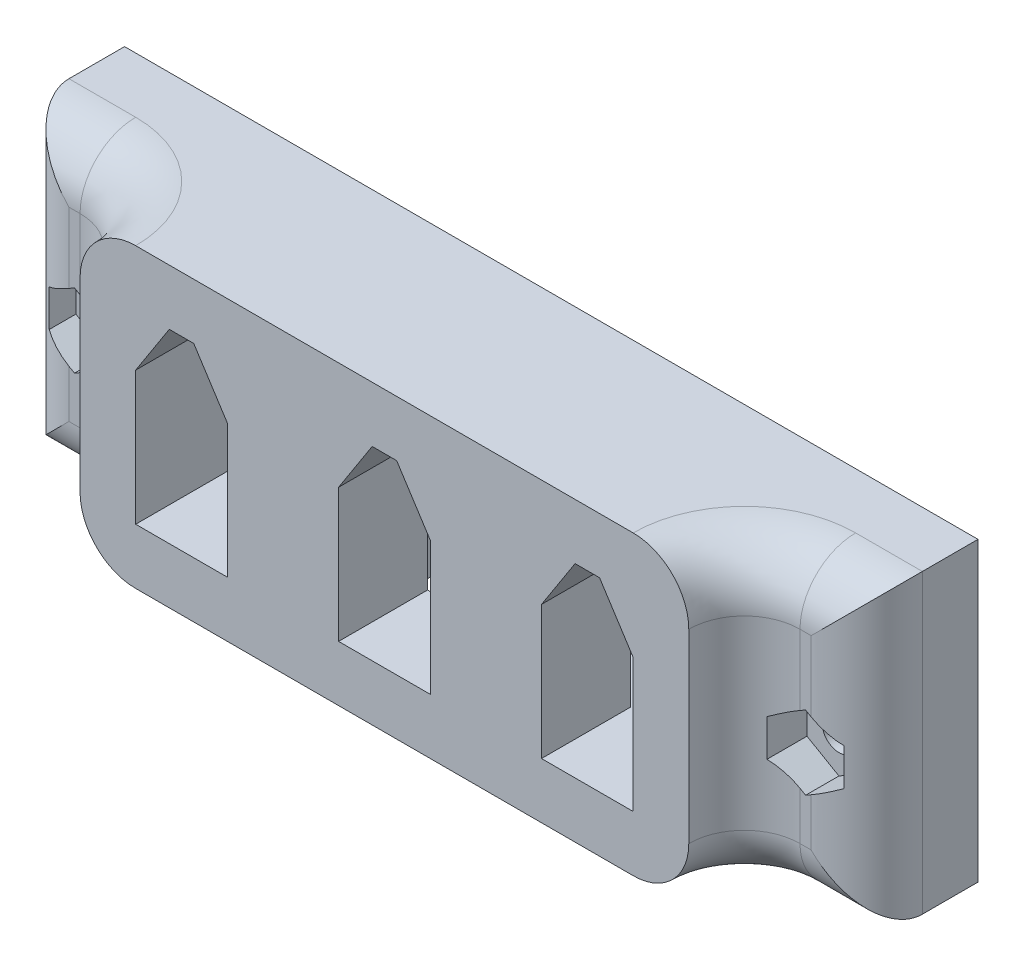
SolidWorks part; units mm, degrees
ref_plane "Front" through (0, 0, 0) normal (0, 0, 1) x (1, 0, 0)
ref_plane "Top" through (0, 0, 0) normal (0, 1, 0) x (1, 0, 0)
ref_plane "Right" through (0, 0, 0) normal (1, 0, 0) x (0, 0, -1)
sketch "Sketch1" plane through (0, 0, 0) normal (0, 0, 1) x (1, 0, 0)
  line L0 (0, 0) -> (0, 12)
  line L1 (0, 12) -> (3.02, 16.686)
  line L3 (8.24, 12) -> (8.24, 0)
  line L4 (0, 0) -> (8.24, 0)
  line L5 (3.02, 16.686) -> (5.22, 16.686)
  line L6 (5.22, 16.686) -> (8.24, 12)
  line L7 (23.46, 16.686) -> (26.48, 12)
  line L8 (26.48, 12) -> (26.48, 0)
  line L9 (18.24, 0) -> (26.48, 0)
  line L10 (18.24, 0) -> (18.24, 12)
  line L11 (18.24, 12) -> (21.26, 16.686)
  line L12 (21.26, 16.686) -> (23.46, 16.686)
  line L13 (41.7, 16.686) -> (44.72, 12)
  line L14 (44.72, 12) -> (44.72, 0)
  line L15 (36.48, 0) -> (44.72, 0)
  line L16 (36.48, 0) -> (36.48, 12)
  line L17 (36.48, 12) -> (39.5, 16.686)
  line L18 (39.5, 16.686) -> (41.7, 16.686)
  line L26 (-16, -5) -> (60.72, -5)
  line L27 (-16, -5) -> (-16, 21.686)
  line L28 (-16, 21.686) -> (60.72, 21.686)
  line L29 (60.72, -5) -> (60.72, 21.686)
  point P9 (4.12, 16.686)
  point P10 (4.12, 0)
  point P25 (22.36, 0)
  point P26 (22.36, -5)
  dimension "D1" = 8.24
  dimension "D2" = 16.686
  dimension "D3" = 2.2
  dimension "D4" = 12
  dimension "D6" = 10
  dimension "D7" = 5
  dimension "D8" = 5
  dimension "D9" = 16
  dimension "D5" = 3
extrude "Boss-Extrude1" add sketch "Sketch1" along normal blind 15
sketch "Sketch2" plane through (0, -5, 0) normal (0, -1, 0) x (-1, 0, 0)
  line L0 (-22.36, -15) -> (-22.36, 0) construction
  line L1 (16, -15) -> (-60.72, -15) construction
  line L2 (16, 0) -> (-60.72, 0) construction
  line L3 (-60.72, -15) -> (-60.72, 0) construction
  line L4 (16, -15) -> (5, -15)
  line L5 (16, -15) -> (16, -10)
  line L6 (16, -10) -> (5, -10)
  line L7 (5, -15) -> (5, -10)
  line L8 (-49.72, -15) -> (-60.72, -15)
  line L9 (-49.72, -15) -> (-49.72, -10)
  line L10 (-49.72, -10) -> (-60.72, -10)
  line L11 (-60.72, -15) -> (-60.72, -10)
  point P19 (0, 0)
  dimension "D1" = 5
  dimension "D2" = 10
extrude "Cut-Extrude1" cut sketch "Sketch2" against normal through all
sketch "Sketch3" plane through (0, 0, 10) normal (0, 0, 1) x (1, 0, 0)
  line L0 (-16, 21.686) -> (-5, 21.686) construction
  line L1 (49.72, 21.686) -> (60.72, 21.686) construction
  circle A0 centre (-10.5, 7.3315) radius 1.5
  circle A1 centre (55.22, 7.3315) radius 1.5
  point P4 (0, 0)
  point P5 (0, 0)
  point P8 (-10.5, 21.686)
  point P9 (0, 0)
  point P12 (55.22, 21.686)
  dimension "D1" = 3
extrude "Cut-Extrude2" cut sketch "Sketch3" against normal blind 25
sketch "Sketch4" plane through (0, 0, 10) normal (0, 0, 1) x (1, 0, 0)
  line L1 (-10.5, 10.6513) -> (-13.375, 8.9914)
  line L2 (-13.375, 8.9914) -> (-13.375, 5.6716)
  line L3 (-13.375, 5.6716) -> (-10.5, 4.0117)
  line L4 (-10.5, 4.0117) -> (-7.625, 5.6716)
  line L5 (-7.625, 5.6716) -> (-7.625, 8.9914)
  line L6 (-7.625, 8.9914) -> (-10.5, 10.6513)
  line L7 (55.22, 10.6513) -> (52.345, 8.9914)
  line L8 (52.345, 8.9914) -> (52.345, 5.6716)
  line L9 (52.345, 5.6716) -> (55.22, 4.0117)
  line L10 (55.22, 4.0117) -> (58.095, 5.6716)
  line L11 (58.095, 5.6716) -> (58.095, 8.9914)
  line L12 (58.095, 8.9914) -> (55.22, 10.6513)
  circle A0 centre (-10.5, 7.3315) radius 2.875 construction
  circle A1 centre (55.22, 7.3315) radius 2.875 construction
  point P10 (-7.625, 7.3315)
  dimension "D1" = 5.75
extrude "Cut-Extrude3" cut sketch "Sketch4" against normal blind 3
sketch "Sketch5" plane through (0, -5, 0) normal (0, -1, 0) x (1, 0, 0)
  line L0 (-16, 0) -> (60.72, 0) construction
  line L1 (0, 7) -> (44.72, 7)
  line L2 (0, 7) -> (0, 0)
  line L3 (0, 0) -> (44.72, 0)
  line L4 (44.72, 7) -> (44.72, 0)
  line L5 (-5, 15) -> (49.72, 15) construction
  dimension "D1" = 8
sketch "Sketch7" plane through (0, 0, 0) normal (0, 0, -1) x (-1, 0, 0)
  line L0 (-44.72, 0) -> (-44.72, 12) construction
  line L1 (0, 0) -> (-12.36, 0)
  line L2 (0, 0) -> (0, 16.686)
  line L3 (0, 16.686) -> (-44.72, 16.686)
  line L4 (-44.72, 0) -> (-44.72, 16.686)
  line L5 (-41.7, 16.686) -> (-39.5, 16.686) construction
  line L6 (0, -5) -> (-44.72, -5) construction
  line L7 (-12.36, -5) -> (-32.36, -5)
  line L8 (-12.36, -5) -> (-12.36, 0)
  line L10 (-32.36, -5) -> (-32.36, 0)
  line L11 (-32.36, 0) -> (-44.72, 0)
  point P15 (-22.36, -5)
  point P16 (-22.36, 16.686)
  dimension "D1" = 20
extrude "Cut-Extrude5" cut sketch "Sketch7" against normal blind 7
fillet "Fillet1" radius 5 8 edges at (60.72, 8.343, 10) (-16, 8.343, 10) (49.72, 8.343, 10) (-5, 8.343, 10) (55.22, 21.686, 10) (55.22, -5, 10) (-10.5, 21.686, 10) (-10.5, -5, 10)
